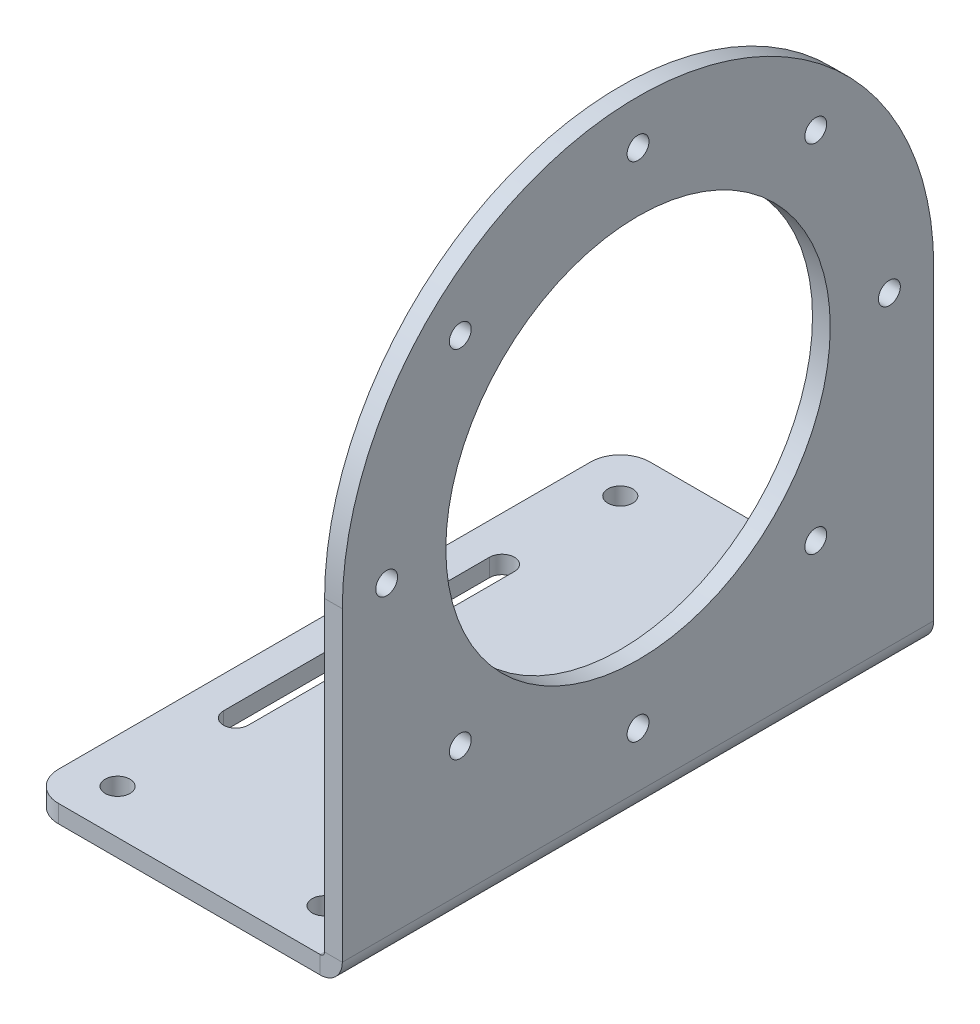
SolidWorks part; units mm, degrees
note: The reader was unsure of these and kept them because the rebuilt part matched: flange length of "边线-法兰1".
material "冷轧钢板 08F"
ref_plane "前视基准面" through (0, 0, 0) normal (0, 0, 1) x (1, 0, 0)
ref_plane "上视基准面" through (0, 0, 0) normal (0, 1, 0) x (1, 0, 0)
ref_plane "右视基准面" through (0, 0, 0) normal (1, 0, 0) x (0, 0, -1)
sketch "草图1" plane through (0, 0, 0) normal (1, 0, 0) x (0, 0, -1)
  line L0 (-50, 0) -> (-50, -55.5)
  line L1 (-50, -55.5) -> (50, -55.5)
  line L2 (50, -55.5) -> (50, 0)
  circle A0 centre (0, 0) radius 42.5 construction
  circle A1 centre (0, 42.5) radius 1.85
  circle A2 centre (30.052, 30.052) radius 1.85
  circle A3 centre (42.5, 0) radius 1.85
  circle A4 centre (30.052, -30.052) radius 1.85
  circle A5 centre (0, -42.5) radius 1.85
  circle A6 centre (-30.052, -30.052) radius 1.85
  circle A7 centre (-42.5, 0) radius 1.85
  circle A8 centre (-30.052, 30.052) radius 1.85
  arc A9 (50, 0) -> (-50, 0) centre (0, 0) ccw
  circle A10 centre (0, 0) radius 32.5
  point P25 (50, 0)
  point P26 (50, 0)
  point P27 (0, -42.5)
  dimension "D1" = 85
  dimension "D2" = 3.7
  dimension "D4" = 100
  dimension "D5" = 65
  dimension "D6" = 13
  dimension "D3" = 8
base flange "基体-法兰1" sketch "草图1" thickness 3 reverse thickness direction no parameters "D1"=0.7366
edge flange "边线-法兰1" sketch "草图8" flange angle 90 flange length 50 flange position material inside bend radius 0.7366 thickness 3 relief rectangular parameters "D6"=10
sketch "草图8" plane through (-3, -55.5, 0) normal (0, -1, 0) x (0, 0, 1)
  line L2 (-50, 0) -> (-50, 50)
  line L3 (-50, 50) -> (50, 50)
  line L4 (50, 50) -> (50, 0)
  line L7 (50, 0) -> (-50, 0) construction
  line L8 (50, 0) -> (-50, 0)
bend "边线折弯1" bend radius 0.7366 bend angle 90 parameters "D5"=1
sketch "草图9" plane through (0, -52.5, 0) normal (0, 1, 0) x (1, 0, 0)
  line L0 (-53, 0) -> (-3, 0) construction
  line L1 (-53, -50) -> (-53, 50) construction
  line L2 (-3, 50) -> (-3, -50) construction
  line L3 (-28.3683, 50) -> (-28.3683, -50) construction
  line L4 (-53, 50) -> (-3.7366, 50) construction
  line L5 (-3.7366, -50) -> (-53, -50) construction
  line L7 (-45.5, -42.5) -> (-10.5, -42.5) construction
  line L8 (-45.5, -42.5) -> (-45.5, 42.5) construction
  line L9 (-45.5, 42.5) -> (-10.5, 42.5) construction
  line L10 (-10.5, -42.5) -> (-10.5, 42.5) construction
  line L11 (-28, 42.5) -> (-28, -42.5) construction
  line L12 (-45.5, 0) -> (-10.5, 0) construction
  circle A0 centre (-45.5, 42.5) radius 2.1
  circle A1 centre (-10.5, 42.5) radius 2.1
  circle A2 centre (-45.5, -42.5) radius 2.1
  circle A3 centre (-10.5, -42.5) radius 2.1
  point P12 (-28, 0)
  dimension "D3" = 4.2
  dimension "D4" = 4.2
  dimension "D5" = 4.2
  dimension "D6" = 4.2
  dimension "D1" = 85
  dimension "D2" = 35
extrude "切除-拉伸1" cut sketch "草图9" against normal blind 10 normal cut yes
fillet "圆角1" radius 5 2 edges at (-53, -54, 50) (-53, -54, -50)
sketch "草图10" plane through (0, -52.5, 0) normal (0, 1, 0) x (1, 0, 0)
  line L0 (-45.5, 22.5) -> (-45.5, -22.5) construction
  line L1 (-43.4, 22.5) -> (-43.4, -22.5)
  line L2 (-47.6, 22.5) -> (-47.6, -22.5)
  line L3 (-10.5, 22.5) -> (-10.5, -22.5) construction
  line L4 (-8.4, 22.5) -> (-8.4, -22.5)
  line L5 (-12.6, 22.5) -> (-12.6, -22.5)
  line L6 (-48, 50) -> (-3.7366, 50) construction
  arc A0 (-43.4, 22.5) -> (-47.6, 22.5) centre (-45.5, 22.5) ccw
  arc A1 (-47.6, -22.5) -> (-43.4, -22.5) centre (-45.5, -22.5) ccw
  arc A2 (-8.4, 22.5) -> (-12.6, 22.5) centre (-10.5, 22.5) ccw
  arc A3 (-12.6, -22.5) -> (-8.4, -22.5) centre (-10.5, -22.5) ccw
  circle A4 centre (-28, 0) radius 2.1
  circle A5 centre (-10.5, 42.5) radius 2.1 construction
  point P3 (-45.5, 0)
  point P8 (-10.5, 0)
  dimension "D5" = 2.1
  dimension "D6" = 2.1
  dimension "D7" = 4.2
  dimension "D8" = 17.5
  dimension "D1" = 45
  dimension "D2" = 45
  dimension "D3" = 22.5
  dimension "D4" = 22.5
  dimension "D9" = 50
extrude "切除-拉伸2" cut sketch "草图10" against normal blind 10 normal cut yes
sketch "折弯-线1" [suppressed] plane through (0, 0, 0) normal (0, 1, 0) x (1, 0, 0)
sketch "边界框1" [suppressed] plane through (0, 0, 0) normal (0, 1, 0) x (1, 0, 0)
sheet metal parameters "钣金6" thickness 3 parameters "D1"=0.7366
flat pattern "平板型式6" [suppressed]
sketch "折弯-线2" plane through (0, 0, 0) normal (0, 1, 0) x (1, 0, 0)
sketch "边界框2" [suppressed] plane through (0, 0, 0) normal (0, 1, 0) x (1, 0, 0)
sheet metal parameters "钣金7" thickness 3 parameters "D1"=0.7366
flat pattern "平板型式6" [suppressed]
sketch "折弯-线2" plane through (0, 0, 0) normal (0, 1, 0) x (1, 0, 0)
sketch "边界框2" [suppressed] plane through (0, 0, 0) normal (0, 1, 0) x (1, 0, 0)
bend of the flat pattern "展平-<边线折弯1>1"
sheet metal parameters "钣金8" thickness 3 parameters "D1"=0.7366
flat pattern "平板型式6" [suppressed]
sketch "折弯-线2" plane through (0, 0, 0) normal (0, 1, 0) x (1, 0, 0)
sketch "边界框2" [suppressed] plane through (0, 0, 0) normal (0, 1, 0) x (1, 0, 0)
bend of the flat pattern "展平-<边线折弯1>1"
sheet metal parameters "钣金9" thickness 3 parameters "D1"=0.7366
flat pattern "平板型式6"
sketch "折弯-线2" plane through (0, 0, 0) normal (1, 0, 0) x (0, 0, -1)
  line L0 (-50, -53.52) -> (50, -53.52) construction
  line L1 (-50, -53.52) -> (50, -53.52) construction
sketch3d "边界框2" [suppressed]
  line L0 (50, -104.54, 0) -> (50, 50, 0) construction
  line L1 (-50, -104.54, 0) -> (-50, 50, 0) construction
  line L2 (50, -104.54, 0) -> (-50, -104.54, 0) construction
  line L3 (50, 50, 0) -> (-50, 50, 0) construction
bend of the flat pattern "展平-<边线折弯1>1"
